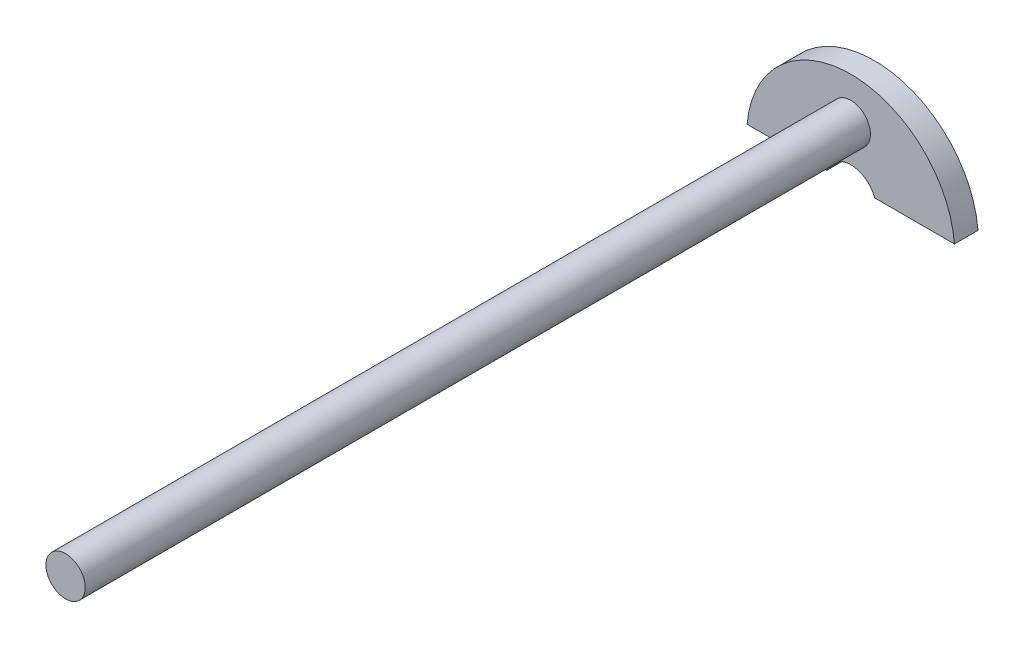
SolidWorks part; units mm, degrees
ref_plane "Front Plane" through (0, 0, 0) normal (0, 0, 1) x (1, 0, 0)
ref_plane "Top Plane" through (0, 0, 0) normal (0, 1, 0) x (1, 0, 0)
ref_plane "Right Plane" through (0, 0, 0) normal (1, 0, 0) x (0, 0, -1)
sketch "Sketch3" plane through (0, 0, 0) normal (0, 0, 1) x (1, 0, 0)
  line L2 (-13.2031, 1.1134) -> (-3.0533, 1.1134)
  line L3 (-13.2054, -1.0866) -> (-3.063, -1.0866)
  line L4 (3.0533, 1.1134) -> (13.2031, 1.1134)
  line L5 (3.063, -1.0866) -> (13.2054, -1.0866)
  circle A0 centre (0, 0) radius 13.25
  circle A1 centre (0, 0) radius 15
  arc A2 (-3.063, -1.0866) -> (3.063, -1.0866) centre (0, 0) ccw
  arc A3 (3.0533, 1.1134) -> (-3.0533, 1.1134) centre (0, 0) ccw
  dimension "D1" = 26.5
  dimension "D2" = 30
  dimension "D3" = 6.5
  dimension "D4" = 10.1498
  dimension "D5" = 10.1424
extrude "BasePlate" add sketch "Sketch3" along normal blind 3 contours A3 L4 A0 L2 region at (0, 6.3995, 0)
sketch "Sketch5" plane through (0, 0, 3) normal (0, 0, 1) x (1, 0, 0)
  line L0 (-13.2031, 1.1134) -> (13.2031, 1.1134) construction
  line L1 (0, 1.1134) -> (0, 14.6134) construction
  circle A3 centre (0, 7.8634) radius 2.5
  dimension "D1" = 5
  dimension "D2" = 6.75
extrude "Rod" add sketch "Sketch5" along normal blind 100
